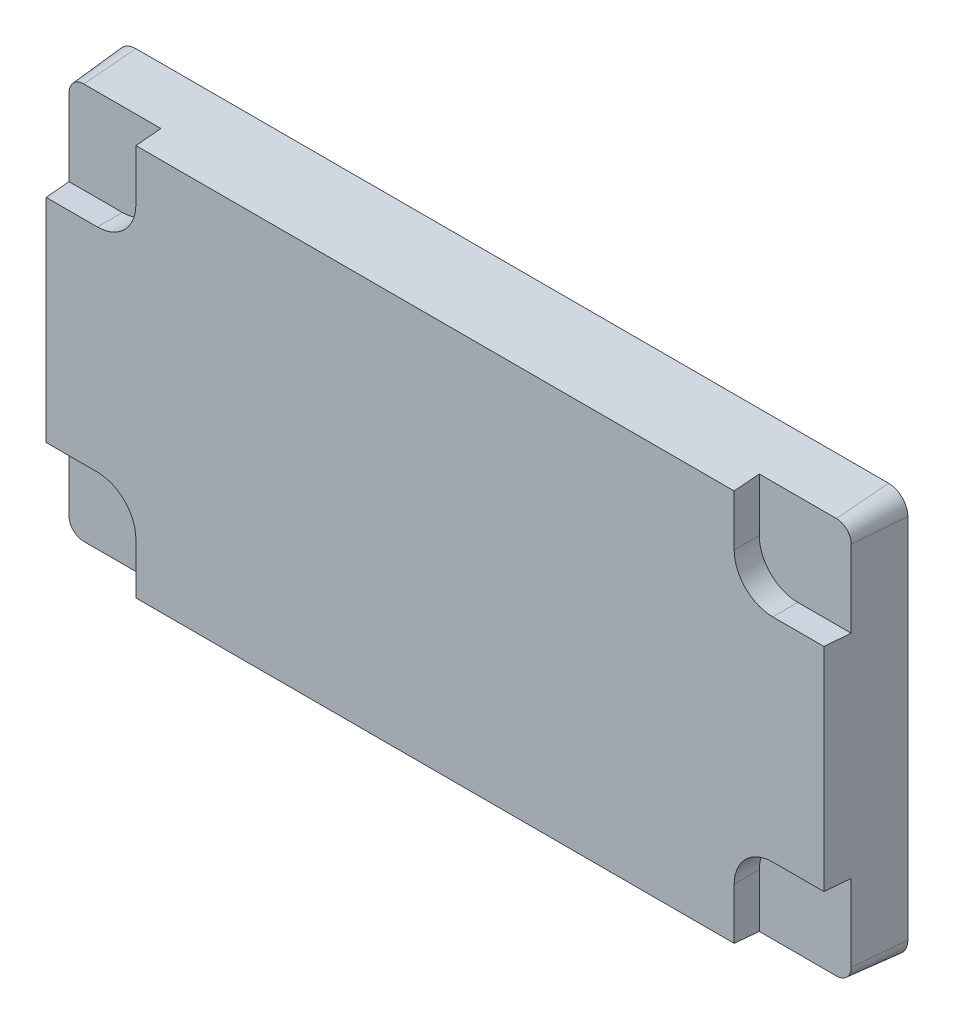
SolidWorks part; units mm, degrees
ref_plane "Plan de face" through (0, 0, 0) normal (0, 0, 1) x (1, 0, 0)
ref_plane "Plan de dessus" through (0, 0, 0) normal (0, 1, 0) x (1, 0, 0)
ref_plane "Plan de droite" through (0, 0, 0) normal (1, 0, 0) x (0, 0, -1)
sketch "Esquisse1" plane through (0, 0, 0) normal (0, 0, 1) x (1, 0, 0)
  line L1 (1, 0) -> (40, 0)
  line L2 (0, 1) -> (0, 20)
  line L3 (1, 21) -> (40, 21)
  line L4 (41, 1) -> (41, 20)
  arc A0 (1, 0) -> (0, 1) centre (1, 1) cw
  arc A1 (40, 0) -> (41, 1) centre (40, 1) ccw
  arc A2 (40, 21) -> (41, 20) centre (40, 20) cw
  arc A3 (0, 20) -> (1, 21) centre (1, 20) cw
  point P7 (0, 0)
  point P12 (41, 21)
  point P15 (0, 21)
  dimension "D3" = 1
  dimension "D1" = 41
  dimension "D2" = 21
extrude "Boss.-Extru.1" add sketch "Esquisse1" along normal blind 4 draft 5
sketch "Esquisse3" plane through (0, 0, 4) normal (0, 0, 1) x (1, 0, 0)
  line L0 (0, 20) -> (0, 1) construction
  line L1 (0, 16) -> (3, 16)
  line L2 (0, 16) -> (0, 21)
  line L3 (0, 21) -> (5, 21)
  line L4 (5, 18) -> (5, 21)
  line L5 (40, 21) -> (1, 21) construction
  line L6 (41, 1) -> (41, 20) construction
  line L7 (41, 16) -> (38, 16)
  line L8 (41, 16) -> (41, 21)
  line L9 (41, 21) -> (36, 21)
  line L10 (36, 18) -> (36, 21)
  line L11 (1, 0) -> (40, 0) construction
  line L12 (41, 5) -> (38, 5)
  line L13 (41, 5) -> (41, 0)
  line L14 (41, 0) -> (36, 0)
  line L15 (36, 3) -> (36, 0)
  line L17 (5, 0) -> (0, 0)
  line L18 (5, 0) -> (5, 3)
  line L19 (3, 5) -> (0, 5)
  line L20 (0, 0) -> (0, 5)
  arc A0 (38, 5) -> (36, 3) centre (38, 3) ccw
  arc A1 (38, 16) -> (36, 18) centre (38, 18) cw
  arc A2 (3, 16) -> (5, 18) centre (3, 18) ccw
  arc A3 (5, 3) -> (3, 5) centre (3, 3) ccw
  dimension "D9" = 2
  dimension "D1" = 5
  dimension "D2" = 5
  dimension "D3" = 5
  dimension "D4" = 5
  dimension "D5" = 5
  dimension "D6" = 5
  dimension "D7" = 5
  dimension "D8" = 5
extrude "Enlèv. mat.-Extru.1" cut sketch "Esquisse3" against normal blind 1.3
shell "Coque1" thickness 1 removed face at (20.5, 10.5, 0)
